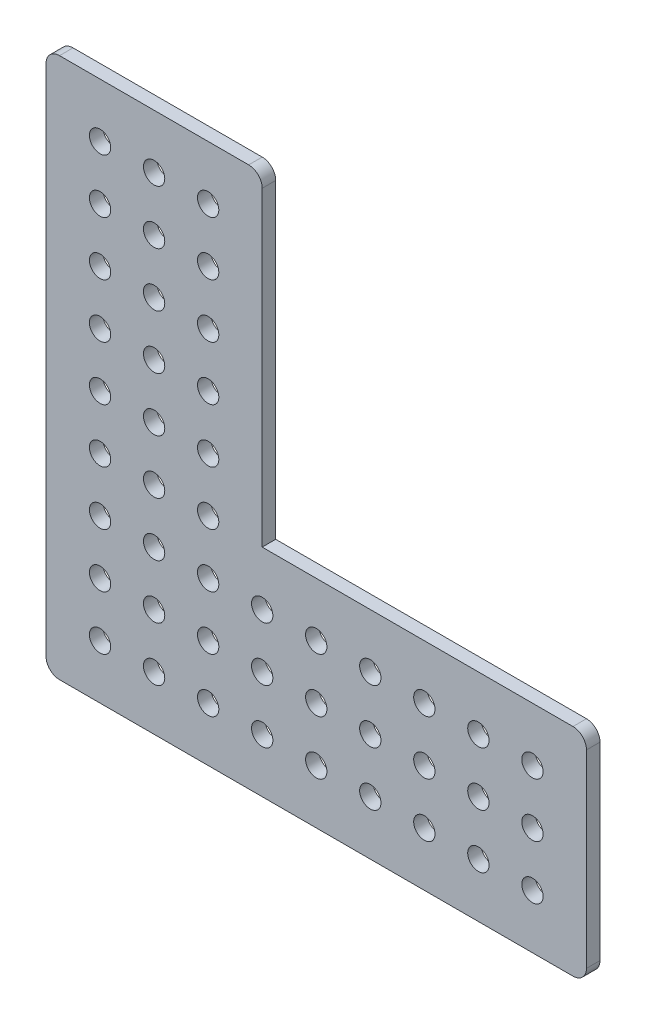
SolidWorks part; units mm, degrees
ref_plane "Front Plane" through (0, 0, 0) normal (0, 0, 1) x (1, 0, 0)
ref_plane "Top Plane" through (0, 0, 0) normal (0, 1, 0) x (1, 0, 0)
ref_plane "Right Plane" through (0, 0, 0) normal (1, 0, 0) x (0, 0, -1)
sketch "Sketch1" plane through (0, 0, 0) normal (0, 0, 1) x (1, 0, 0)
  line L1 (-101.0024, 5.3233) -> (22.8226, 5.3233)
  line L2 (-101.0024, 5.3233) -> (-101.0024, -42.3017)
  line L3 (-97.8274, -45.4767) -> (22.8226, -45.4767)
  line L4 (25.9976, 2.1483) -> (25.9976, -42.3017)
  line L6 (-101.0024, 5.3233) -> (-101.0024, 78.3483)
  line L7 (-97.8274, 81.5233) -> (-53.3774, 81.5233)
  line L8 (-50.2024, 5.3233) -> (-50.2024, 78.3483)
  arc A0 (-101.0024, -42.3017) -> (-97.8274, -45.4767) centre (-97.8274, -42.3017) ccw
  arc A1 (22.8226, -45.4767) -> (25.9976, -42.3017) centre (22.8226, -42.3017) ccw
  arc A2 (22.8226, 5.3233) -> (25.9976, 2.1483) centre (22.8226, 2.1483) cw
  arc A3 (-53.3774, 81.5233) -> (-50.2024, 78.3483) centre (-53.3774, 78.3483) cw
  arc A4 (-101.0024, 78.3483) -> (-97.8274, 81.5233) centre (-97.8274, 78.3483) cw
  point P7 (0, 0)
  point P8 (-101.0024, 5.3233)
  point P11 (-101.0024, -45.4767)
  point P14 (25.9976, -45.4767)
  point P17 (25.9976, 5.3233)
  point P20 (-50.2024, 81.5233)
  point P23 (-101.0024, 81.5233)
  dimension "D5" = 3.175
  dimension "D1" = 50.8
  dimension "D2" = 127
  dimension "D3" = 50.8
  dimension "D4" = 76.2
extrude "Boss-Extrude1" add sketch "Sketch1" along normal blind 3.175 contours L1 L8 L7 L6 | L4 L1 L2 L3 region at (-75.6024, 43.3814, 0) region at (-37.5235, -20.0684, 0)
sketch "Sketch2" plane through (0, 0, 3.175) normal (0, 0, 1) x (1, 0, 0)
  line L0 (-97.8274, 81.5233) -> (-53.3774, 81.5233) construction
  line L1 (-101.0024, -42.3017) -> (-101.0024, 78.3483) construction
  line L2 (25.9976, 2.1483) -> (25.9976, -42.3017) construction
  line L4 (-50.2024, 5.3233) -> (22.8226, 5.3233) construction
  circle A0 centre (-88.3024, 68.8233) radius 2.505
  circle A1 centre (13.2976, -7.3767) radius 2.505
  circle A2 centre (-75.6024, 68.8233) radius 2.505
  circle A3 centre (-62.9024, 68.8233) radius 2.505
  circle A4 centre (-75.6024, 56.1233) radius 2.505
  circle A5 centre (-62.9024, 56.1233) radius 2.505
  circle A6 centre (-75.6024, 43.4233) radius 2.505
  circle A7 centre (-62.9024, 43.4233) radius 2.505
  circle A8 centre (-75.6024, 30.7233) radius 2.505
  circle A9 centre (-62.9024, 30.7233) radius 2.505
  circle A10 centre (-75.6024, 18.0233) radius 2.505
  circle A11 centre (-62.9024, 18.0233) radius 2.505
  circle A12 centre (-75.6024, 5.3233) radius 2.505
  circle A13 centre (-62.9024, 5.3233) radius 2.505
  circle A24 centre (-88.3024, 56.1233) radius 2.505
  circle A25 centre (-88.3024, 43.4233) radius 2.505
  circle A26 centre (-88.3024, 30.7233) radius 2.505
  circle A27 centre (-88.3024, 18.0233) radius 2.505
  circle A28 centre (-88.3024, 5.3233) radius 2.505
  circle A29 centre (-88.3024, -7.3767) radius 2.505
  circle A30 centre (-88.3024, -20.0767) radius 2.505
  circle A31 centre (-88.3024, -32.7767) radius 2.505
  circle A34 centre (0.5976, -7.3767) radius 2.505
  circle A35 centre (-12.1024, -7.3767) radius 2.505
  circle A36 centre (-24.8024, -7.3767) radius 2.505
  circle A37 centre (-37.5024, -7.3767) radius 2.505
  circle A38 centre (-50.2024, -7.3767) radius 2.505
  circle A39 centre (-62.9024, -7.3767) radius 2.505
  circle A40 centre (-75.6024, -7.3767) radius 2.505
  circle A41 centre (0.5976, -20.0767) radius 2.505
  circle A42 centre (-12.1024, -20.0767) radius 2.505
  circle A43 centre (-24.8024, -20.0767) radius 2.505
  circle A44 centre (-37.5024, -20.0767) radius 2.505
  circle A45 centre (-50.2024, -20.0767) radius 2.505
  circle A46 centre (-62.9024, -20.0767) radius 2.505
  circle A47 centre (-75.6024, -20.0767) radius 2.505
  circle A48 centre (0.5976, -32.7767) radius 2.505
  circle A49 centre (-12.1024, -32.7767) radius 2.505
  circle A50 centre (-24.8024, -32.7767) radius 2.505
  circle A51 centre (-37.5024, -32.7767) radius 2.505
  circle A52 centre (-50.2024, -32.7767) radius 2.505
  circle A53 centre (-62.9024, -32.7767) radius 2.505
  circle A54 centre (-75.6024, -32.7767) radius 2.505
  circle A55 centre (13.2976, -20.0767) radius 2.505
  circle A56 centre (13.2976, -32.7767) radius 2.505
  dimension "D1" = 5.01
  dimension "D2" = 5.01
  dimension "D3" = 12.7
  dimension "D4" = 12.7
  dimension "D7" = 12.7
  dimension "D8" = 12.7
  dimension "D9" = 8
  dimension "D10" = 3
extrude "Cut-Extrude1" cut sketch "Sketch2" against normal through all
